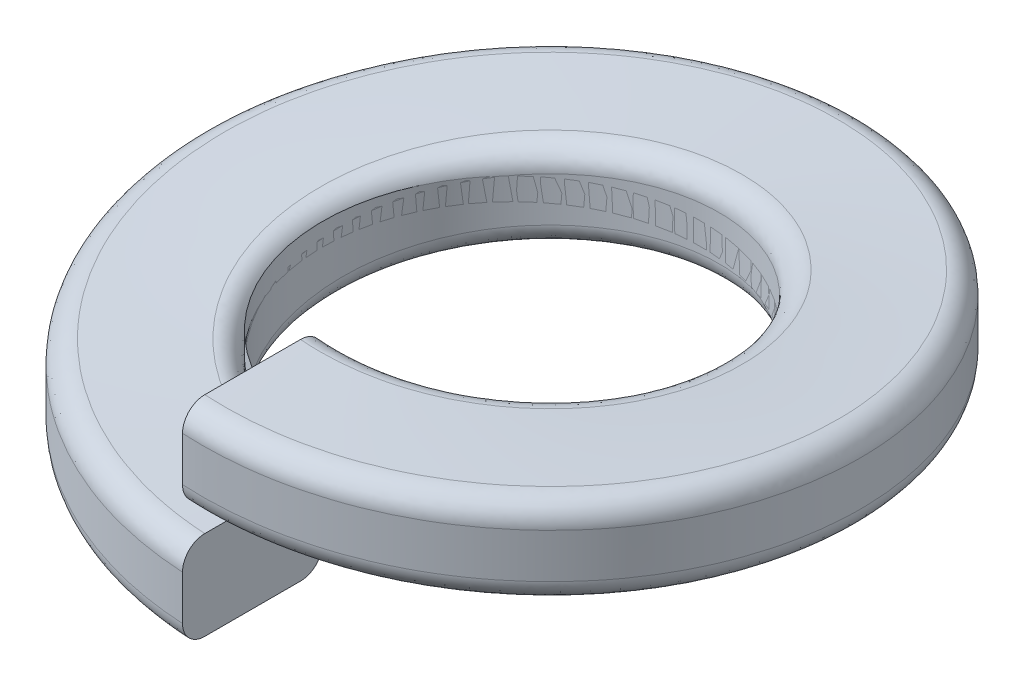
SolidWorks part; units mm, degrees
material "Cast Stainless Steel"
ref_plane "Front Plane" through (0, 0, 0) normal (0, 0, 1) x (1, 0, 0)
ref_plane "Top Plane" through (0, 0, 0) normal (0, 1, 0) x (1, 0, 0)
ref_plane "Right Plane" through (0, 0, 0) normal (1, 0, 0) x (0, 0, -1)
sketch "Sketch1" plane through (0, 0, 0) normal (0, 1, 0) x (1, 0, 0)
  circle A0 centre (0, 0) radius 4.25
  dimension "D1" = 8.5
curve "Helix/Spiral1" pitch 2.7 height 2.7 turns 1
sketch "Sketch2" plane through (0, 0, 0) normal (1, 0, 0) x (0, 0, -1)
  line L1 (-4.25, 0) -> (-7.4, 0)
  line L2 (-4.25, 0) -> (-4.25, 2)
  line L3 (-4.25, 2) -> (-7.4, 2)
  line L4 (-7.4, 0) -> (-7.4, 2)
  dimension "D1" = 3.15
  dimension "D2" = 2
sweep "Sweep1" add profiles "Sketch2" path "Helix/Spiral1"
fillet "Fillet1" radius 0.5 4 edges
sketch "Sketch3" plane through (0, 0, 0) normal (0, 1, 0) x (1, 0, 0)
  circle A0 centre (0, 0) radius 4.25
  dimension "D1" = 8.5
surface "Surface-Extrude1" sketch "Sketch3" parameters "D1"=0.5, "D19"=2
equation "\"d1\"= 8.5"
equation "\"d2\"= 14.8"
equation "\"h\"= 4.7"
equation "\"s\"= 2"
equation "\"D1@Sketch1\"=\"d1\""
equation "\"D3@Helix/Spiral1\"=\"h\"-\"s\""
equation "\"D1@Sketch2\"=(\"d2\"-\"d1\")/2"
equation "\"D2@Sketch2\"=\"s\""
equation "\"r\"= 0.5"
equation "\"D1@Fillet1\"=\"r\""
